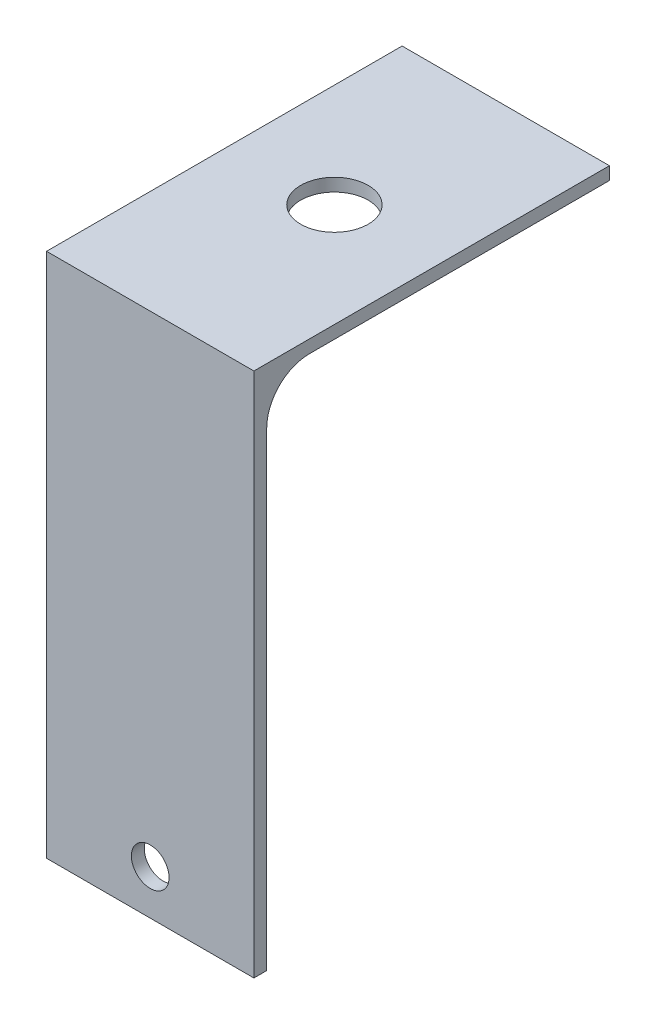
SolidWorks part; units mm, degrees
material "1060 Alloy"
ref_plane "Front Plane" through (0, 0, 0) normal (0, 0, 1) x (1, 0, 0)
ref_plane "Top Plane" through (0, 0, 0) normal (0, 1, 0) x (1, 0, 0)
ref_plane "Right Plane" through (0, 0, 0) normal (1, 0, 0) x (0, 0, -1)
sketch "Sketch1" plane through (0, 0, 0) normal (0, 0, 1) x (1, 0, 0)
  line L1 (12.1, -30.68) -> (-12.1, -30.68)
  line L2 (12.1, -30.68) -> (12.1, 30.68)
  line L3 (12.1, 30.68) -> (-12.1, 30.68)
  line L4 (-12.1, -30.68) -> (-12.1, 30.68)
  line L5 (12.1, -30.68) -> (-12.1, 30.68) construction
  line L6 (12.1, 30.68) -> (-12.1, -30.68) construction
  point P0 (0, 0)
  dimension "Base" = 24.2
  dimension "ServoToTop" = 61.36
extrude "Boss-Extrude1" add sketch "Sketch1" along normal blind 1.5
sketch "Sketch2" plane through (0, 0, 1.5) normal (0, 0, 1) x (1, 0, 0)
  line L0 (-12.1, -30.68) -> (12.1, -30.68) construction
  line L1 (12.1, -30.68) -> (12.1, 30.68) construction
  circle A0 centre (0, -25.48) radius 2.2
  dimension "D2" = 4.4
  dimension "D1" = 5.2
  dimension "D3" = 12.1
extrude "Cut-Extrude1" cut sketch "Sketch2" against normal through all
sketch "Sketch4" plane through (0, 30.68, 0) normal (0, 1, 0) x (1, 0, 0)
  line L0 (-12.1, -1.5) -> (-12.1, 0) construction
  line L1 (-12.1, 0) -> (12.1, 0)
  line L2 (-12.1, 0) -> (-12.1, 40)
  line L3 (-12.1, 40) -> (12.1, 40)
  line L4 (12.1, 0) -> (12.1, 40)
  line L5 (12.1, -1.5) -> (12.1, 0) construction
  dimension "BaseTopLength" = 40
extrude "Boss-Extrude2" add sketch "Sketch4" against normal blind 1.5
sketch "Sketch5" plane through (0, 29.18, 0) normal (0, -1, 0) x (1, 0, 0)
  line L0 (-12.1, 0) -> (12.1, 0) construction
  line L1 (-12.1, -40) -> (-12.1, 0) construction
  circle A0 centre (0, -20) radius 3.937
  dimension "D1" = 7.874
  dimension "D2" = 20
  dimension "D3" = 12.1
extrude "Cut-Extrude2" cut sketch "Sketch5" against normal through all
fillet "Fillet1" radius 5 1 edges at (0, 29.18, 0) type face fillet first side face at (0, 29.18, -23.937) second side face at (2.2, -25.48, 0)
